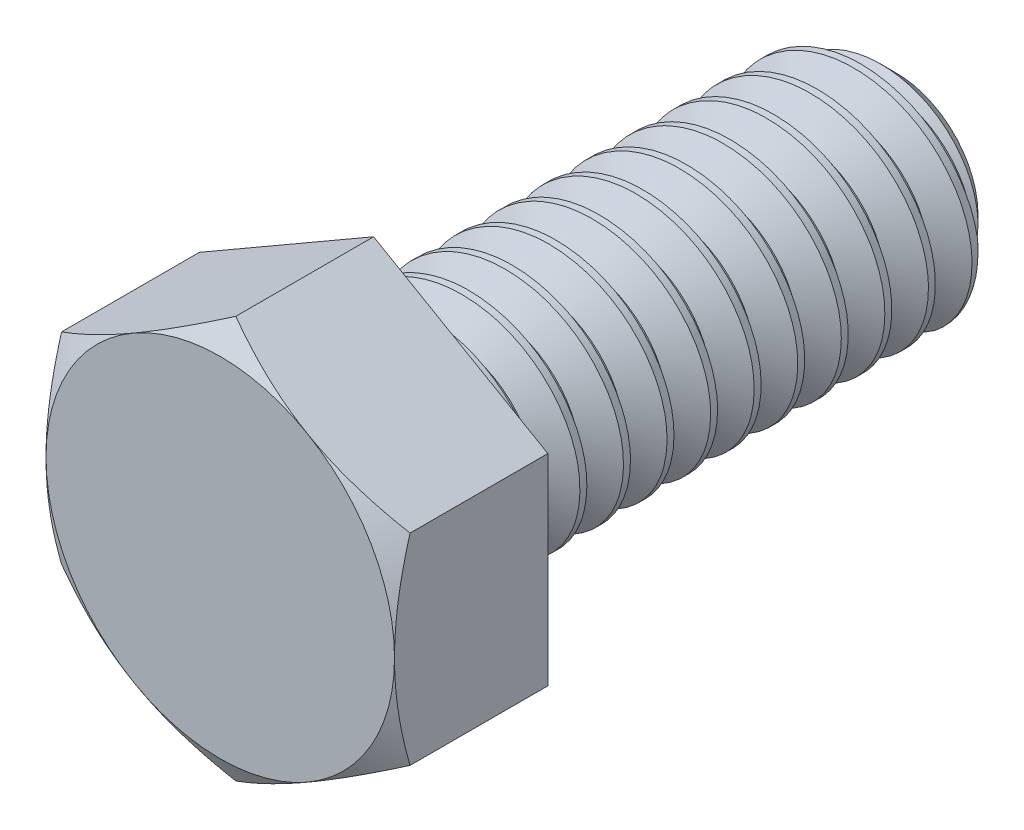
SolidWorks part; units mm, degrees
ref_plane "Front" through (0, 0, 0) normal (0, 0, 1) x (1, 0, 0)
ref_plane "Top" through (0, 0, 0) normal (0, 1, 0) x (1, 0, 0)
ref_plane "Right" through (0, 0, 0) normal (1, 0, 0) x (0, 0, -1)
sketch "Sketch1" plane through (0, 0, 0) normal (0, 0, 1) x (1, 0, 0)
  line L1 (-3.175, -1.8331) -> (0, -3.6662)
  line L2 (0, -3.6662) -> (3.175, -1.8331)
  line L3 (3.175, -1.8331) -> (3.175, 1.8331)
  line L4 (3.175, 1.8331) -> (0, 3.6662)
  line L5 (0, 3.6662) -> (-3.175, 1.8331)
  line L6 (-3.175, 1.8331) -> (-3.175, -1.8331)
  circle A0 centre (0, 0) radius 3.175 construction
  circle A1 centre (0, 0) radius 3.175 construction
  dimension "Head Dia" = 6.35
extrude "Extrude3" add sketch "Sketch1" along normal blind 2.794
sketch "Sketch4" plane through (0, 0, 0) normal (1, 0, 0) x (0, 0, -1)
  line L0 (0, 0) -> (9.525, 0)
  line L3 (9.525, 0) -> (9.525, 2.0828)
  line L4 (9.525, 2.0828) -> (0, 2.0828)
  line L6 (0, 2.0828) -> (0, 0)
  line L9 (9.525, 2.0828) -> (9.525, -2.0828) construction
  dimension "length" = 9.525
  dimension "dia" = 4.1656
revolve "Revolve1" add sketch "Sketch4" angle 360 about L0
sketch "Sketch13" plane through (0, 0, -9.525) normal (0, 0, -1) x (-1, 0, 0)
  circle A2 centre (0, 0) radius 2.0828
curve "Helix/Spiral1" pitch 0.7937 height 12.319 radius 2.0828 centre (0, 0, -9.525) axis (0, 0, 1) start towards (1, 0, 0)
chamfer "Chamfer2" distance 0.5953 angle 45 1 edges at (2.0828, 0, -9.525)
sketch "Sketch14" plane through (0, 0, 0) normal (1, 0, 0) x (0, 0, -1)
  line L0 (9.525, 2.1076) -> (10.2195, 2.1076)
  line L1 (10.2195, 2.1076) -> (9.9219, 1.5706)
  line L2 (9.9219, 1.5706) -> (9.8227, 1.5706)
  line L3 (9.8227, 1.5706) -> (9.525, 2.1076)
  line L4 (9.6738, 1.8391) -> (10.0707, 1.8391) construction
  dimension "D1" = 0.0992
  dimension "D2" = 58
  dimension "D3" = 0.3969
  dimension "D4" = 0.0248
sweep "Cut-Sweep1" cut profiles "Sketch14" path "Helix/Spiral1" align with end faces yes
ref_plane "Plane1" through (0, 0, 28.575) normal (0, 0, -1) x (-1, 0, 0)
sketch "Sketch29" [suppressed] plane through (0, 0, 28.575) normal (0, 0, -1) x (-1, 0, 0)
  circle A0 centre (0, 0) radius 1.7526 construction
  circle A1 centre (0, 0) radius 1.7526
  point P3 (0, -1.7526)
  point P4 (0, 1.7526)
extrude "Extrude11" [suppressed] add sketch "Sketch29" against normal up to surface (28.575 mm away) up to plane "Front"
sketch "Sketch26" plane through (0, 0, 0) normal (0, 0, 1) x (1, 0, 0)
  circle A1 centre (0, 0) radius 0.5461
  dimension "D1" = 1.0922
extrude "Extrude12" add sketch "Sketch26" along normal up to surface (2.794 mm away) up to face at (0, 0, 2.794)
sketch "Sketch30" plane through (0, 0, 2.794) normal (0, 0, 1) x (1, 0, 0)
  circle A0 centre (0, 0) radius 3.175 construction
  circle A1 centre (0, 0) radius 3.175
extrude "Extrude13" cut sketch "Sketch30" against normal blind 2.54 draft 60 flip side to cut
sketch "Sketch18" plane through (0, 0, 0) normal (1, 0, 0) x (0, 0, -1)
  line L0 (-2.5104, 3.6662) -> (0, 3.6662) construction
  line L1 (9.525, 2.0828) -> (0, 2.0828) construction
  line L2 (-2.794, 3.175) -> (-2.794, 2.7496) construction
  line L3 (0, 3.6662) -> (0, 1.8331) construction
  point P0 (8.3344, -2.0828)
  point P1 (8.7313, 2.0828)
  point P2 (-2.794, 3.6662)
  point P9 (0, 3.6662)
  dimension "D1" = 0.7937
  dimension "D2" = 1.1906
equation "\"D3@Helix/Spiral1\" = \"length@Sketch4\" + \"Head Ht@Extrude3\""
equation "\"D1@Sketch14\" = \"D4@Helix/Spiral1\" * .125"
equation "\"D3@Sketch14\" = \"D4@Helix/Spiral1\" * .5"
equation "\"D4@Sketch14\" = \"D1@Sketch14\" * .25"
equation "\"D1@Chamfer2\" = \"D4@Helix/Spiral1\" * .75"
equation "\"D1@Sketch18\" = \"D4@Helix/Spiral1\""
equation "\"D2@Sketch18\" = \"D4@Helix/Spiral1\" * 1.5"
